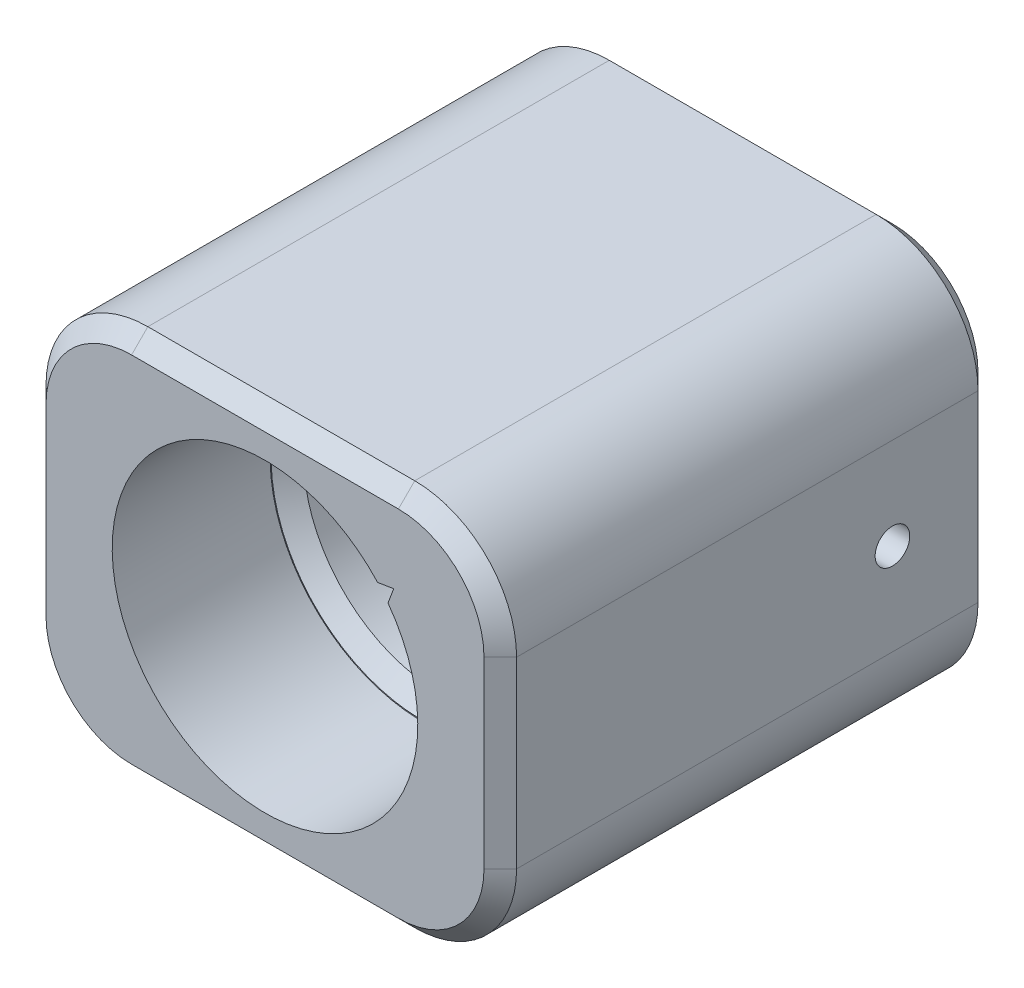
SolidWorks part; units mm, degrees
ref_plane "Front Plane" through (0, 0, 0) normal (0, 0, 1) x (1, 0, 0)
ref_plane "Top Plane" through (0, 0, 0) normal (0, 1, 0) x (1, 0, 0)
ref_plane "Right Plane" through (0, 0, 0) normal (1, 0, 0) x (0, 0, -1)
sketch "Sketch1" plane through (0, 0, 0) normal (1, 0, 0) x (0, 0, -1)
  line L0 (0, 0) -> (0, 13.3)
  line L1 (0, 13.3) -> (-33, 13.3)
  line L2 (-33, 13.3) -> (-33, 15)
  line L3 (-33, 15) -> (-48.5, 15)
  line L4 (-48.5, 15) -> (-48.5, 0)
  line L5 (-48.5, 0) -> (0, 0)
  line L6 (-1000, 0) -> (49000, 0) construction
  point P7 (0, 0)
  point P10 (0, 0)
  point P11 (0, 0)
  dimension "D1" = 13.3
  dimension "D2" = 15
  dimension "D3" = 15.5
  dimension "D4" = 33
sketch "Sketch2" plane through (0, 0, 0) normal (0, 0, 1) x (1, 0, 0)
  line L1 (-23.1, -19) -> (23.1, -19)
  line L2 (-23.1, -19) -> (-23.1, 19)
  line L3 (-23.1, 19) -> (23.1, 19)
  line L4 (23.1, -19) -> (23.1, 19)
  line L5 (0, 19) -> (0, -19) construction
  line L6 (-23.1, 0) -> (23.1, 0) construction
  line L7 (15.7, -3.5) -> (19.1, -3.5) construction
  line L8 (15.7, -3.5) -> (15.7, 3.5) construction
  line L9 (15.7, 3.5) -> (19.1, 3.5) construction
  line L10 (19.1, -3.5) -> (19.1, 3.5) construction
  line L11 (17.4, 3.5) -> (17.4, -3.5) construction
  line L12 (15.7, 0) -> (19.1, 0) construction
  circle A0 centre (0, 0) radius 15 construction
  circle A1 centre (0, 0) radius 13.3
  circle A2 centre (0, 0) radius 19 construction
  point P11 (17.4, 0)
  point P15 (13.3, 0)
  point P16 (0, 0)
  point P17 (0, 0)
  dimension "D2" = 3.4
  dimension "D3" = 2.4
  dimension "D4" = 4
  dimension "D5" = 7
  dimension "D1" = 4
extrude "Boss-Extrude1" add sketch "Sketch2" along normal up to vertex (48.5 mm away) up to point (0, 0, 48.5)
sketch "Sketch3" plane through (23.1, 0, 0) normal (1, 0, 0) x (0, 0, -1)
  line L0 (-48.5, 0) -> (0, 0) construction
  line L1 (-16, -3.5) -> (-4, -3.5) construction
  line L2 (-16, -3.5) -> (-16, 3.5) construction
  line L3 (-16, 3.5) -> (-4, 3.5) construction
  line L4 (-4, -3.5) -> (-4, 3.5) construction
  line L5 (-10, 3.5) -> (-10, -3.5) construction
  line L6 (-16, 0) -> (-4, 0) construction
  line L7 (0, 0) -> (0, 13.3) construction
  circle A0 centre (-10, 0) radius 1.7
  point P0 (-10, 0)
  point P10 (0, 0)
  dimension "D3" = 3.4
  dimension "D1" = 12
  dimension "D2" = 10
extrude "Cut-Extrude1" cut sketch "Sketch3" against normal through all
sketch "Sketch4" plane through (0, 0, 0) normal (0, 0, -1) x (-1, 0, 0)
  line L0 (0, -1000) -> (0, 49000) construction
  line L1 (-15.7, -3.5) -> (-19.1, -3.5) construction
  line L2 (-15.7, -3.5) -> (-15.7, 3.5) construction
  line L3 (-15.7, 3.5) -> (-19.1, 3.5) construction
  line L4 (-19.1, -3.5) -> (-19.1, 3.5) construction
  line L5 (-15.7, -3.5) -> (-19.1, -3.5)
  line L6 (-15.7, -3.5) -> (-15.7, 3.5)
  line L7 (-15.7, 3.5) -> (-19.1, 3.5)
  line L8 (-19.1, -3.5) -> (-19.1, 3.5)
  line L9 (19.1, -3.5) -> (19.1, 3.5)
  line L10 (15.7, 3.5) -> (19.1, 3.5)
  line L11 (15.7, -3.5) -> (15.7, 3.5)
  line L12 (15.7, -3.5) -> (19.1, -3.5)
extrude "Cut-Extrude2" cut sketch "Sketch4" against normal up to vertex (16 mm away) up to point (23.1, 0, 16)
revolve "Cut-Revolve1" cut sketch "Sketch1" angle 360 about L6
sketch "Sketch5" plane through (0, 0, 48.5) normal (0, 0, 1) x (1, 0, 0)
  line L0 (12.6384, 10.3952) -> (11.0601, 10.1329)
  line L1 (11.0601, 10.1329) -> (12.0764, 8.8972)
  line L2 (12.0764, 8.8972) -> (12.6384, 10.3952)
  line L3 (0, 0) -> (23.1, 19) construction
  circle A0 centre (0, 0) radius 15 construction
  point P5 (0, 0)
  point P6 (0, 0)
  point P9 (0, 0)
  point P10 (11.5683, 9.515)
  point P13 (0, 0)
  dimension "D1" = 1.6
extrude "Cut-Extrude3" cut sketch "Sketch5" against normal up to surface (15.5 mm away) up to face at (15, 0, 33)
sketch "Sketch6" plane through (0, 0, 33) normal (0, 0, 1) x (1, 0, 0)
  line L0 (11.3234, 9.3136) -> (9.745, 9.0512)
  line L1 (9.745, 9.0512) -> (10.7614, 7.8155)
  line L2 (10.7614, 7.8155) -> (11.3234, 9.3136)
  line L3 (12.0764, 8.8972) -> (12.6384, 10.3952) construction
  line L4 (0, 0) -> (23.1, 19) construction
  circle A0 centre (0, 0) radius 13.3 construction
  point P5 (0, 0)
  point P8 (10.2532, 8.4334)
  point P11 (0, 0)
extrude "Cut-Extrude4" cut sketch "Sketch6" against normal through all
fillet "Fillet1" radius 10 4 edges at (23.1, -19, 24.25) (-23.1, -19, 24.25) (-23.1, 19, 24.25) (23.1, 19, 24.25)
chamfer "Chamfer1" distance 1.6 angle 45 8 edges at (0, -19, 48.5) (20.1711, -16.0711, 48.5) (-20.1711, -16.0711, 48.5) (23.1, 0, 48.5) (-23.1, 0, 48.5) (20.1711, 16.0711, 48.5) (-20.1711, 16.0711, 48.5) (0, 19, 48.5)
chamfer "Chamfer2" distance 1.6 angle 45 1 edges at (-10.2718, -8.4487, 33)
chamfer "Chamfer3" distance 1.6 angle 45 8 edges at (-19.1, 0, 0) (-17.4, -3.5, 0) (-15.7, 0, 0) (-17.4, 3.5, 0) (17.4, -3.5, 0) (15.7, 0, 0) (19.1, 0, 0) (17.4, 3.5, 0)
chamfer "Chamfer4" distance 1.6 angle 45 8 edges at (0, -19, 0) (20.1711, -16.0711, 0) (-20.1711, -16.0711, 0) (23.1, 0, 0) (-23.1, 0, 0) (20.1711, 16.0711, 0) (-20.1711, 16.0711, 0) (0, 19, 0)
